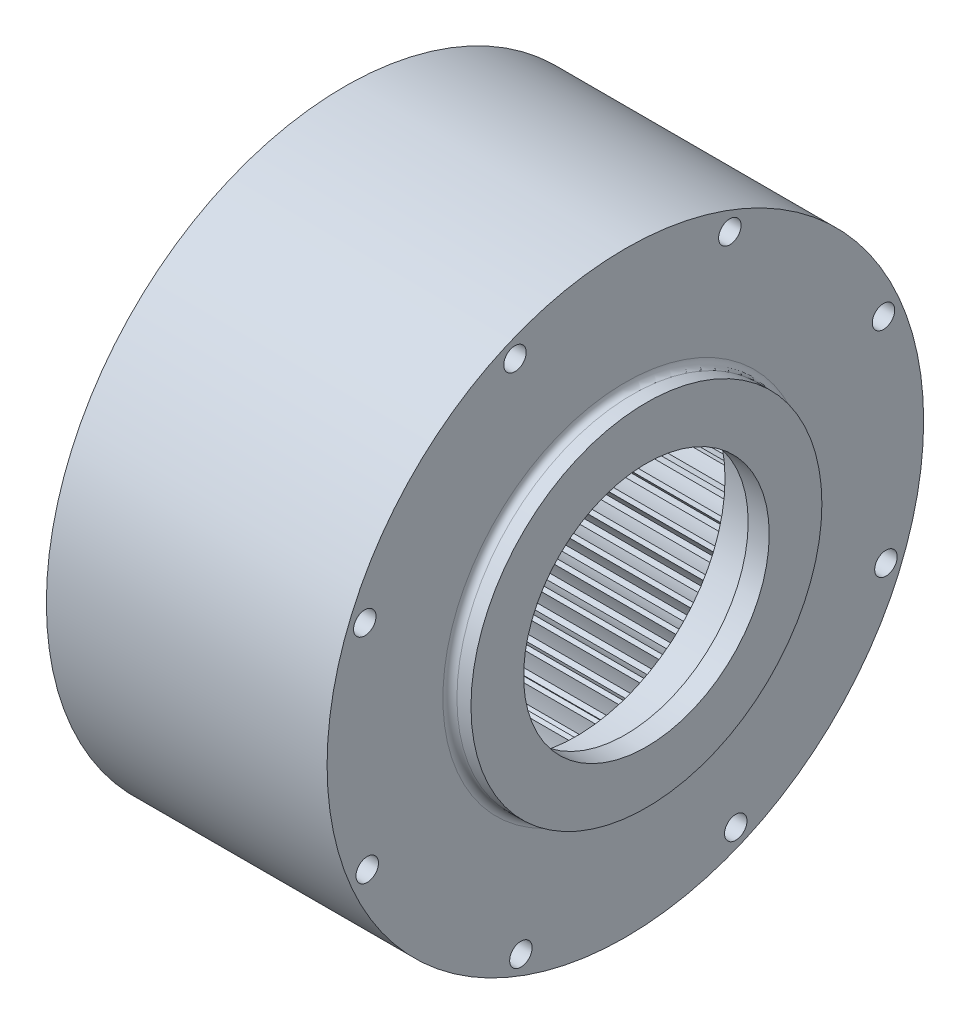
SolidWorks part; units mm, degrees
ref_plane "Plane1" through (0, 0, 0) normal (0, 0, 1) x (1, 0, 0)
ref_plane "Plane2" through (0, 0, 0) normal (0, 1, 0) x (1, 0, 0)
ref_plane "Plane3" through (0, 0, 0) normal (1, 0, 0) x (0, 0, -1)
sketch "HoldingSke" plane through (0, 0, 0) normal (0, 1, 0) x (1, 0, 0)
  line L0 (0, 0) -> (0.342, -0.9397)
  line L1 (-15, 0) -> (100, 0) construction
  line L2 (0, 0) -> (-2.1039, 2.3779)
  line L3 (0, 0) -> (-11.863, 4.5341)
  line L4 (0, 0) -> (2.9537, 8.1152)
  line L5 (0, 0) -> (-23.7986, -8.8762)
  line L6 (0, 0) -> (-10.5278, -7.1032)
  line L7 (-2.1039, 2.3779) -> (3.3635, 27.1825)
  line L8 (-76.2, 3.3779) -> (-54.61, 3.3779)
  line L9 (-71.009, 38.7566) -> (-53.1078, 45.2721)
  line L10 (-76.2, 71.12) -> (104.1128, 71.12)
  line L11 (0, 0) -> (-30, 0)
  line L12 (-76.2, 101.6) -> (-76.162, 101.6)
  line L13 (24.9733, 27.94) -> (52.9518, 28.4284)
  line L14 (24.9733, 27.94) -> (24.9743, 27.94)
  line L15 (24.9733, 27.94) -> (100.4006, 29.5858)
  circle A0 centre (0, 0) radius 42.5
  circle A1 centre (0, 0) radius 12.7
  circle A2 centre (0, 0) radius 12.7
  dimension "MHD" = 25.4
  dimension "Hub_dia" = 25.4
  dimension "Diameter" = 85
  dimension "Num_teeth" = 70
  dimension "Pitch" = 1
  dimension "Overall_len" = 25.4
  dimension "Show_teeth" = 70
  dimension "Thickness" = 12.7
  dimension "OAL" = 25.4001
  dimension "T_dim" = 21.59
  dimension "Ap" = 20
  dimension "H" = 19.05
  dimension "Pitch_radius" = 180.3128
  dimension "Width" = 30
  dimension "Backlash" = 0.038
  dimension "Addendum_fac" = 1
  dimension "Dedendum_fac" = 1.25
  dimension "Clearance_fac" = 0.25
  dimension "Dedendum_add" = 0.001
  dimension "Module" = 1
sketch "BasProSke" plane through (0, 0, 0) normal (0, 1, 0) x (1, 0, 0)
  line L0 (-10, 0) -> (60, 0) construction
  line L1 (0, 34) -> (0, 42.5)
  line L2 (0, 34) -> (30, 34)
  line L3 (30, 34) -> (30, 42.5)
  line L4 (30, 42.5) -> (0, 42.5)
  dimension "Diameter" = 85
  dimension "Thickness" = 30
  dimension "Inside_diameter" = 68
revolve "Base-Revolve" add sketch "BasProSke" angle 360 about L0
sketch "TooCutSke" plane through (0, 0, 0) normal (1, 0, 0) x (0, 0, -1)
  line L3 (0.8803, 34.9889) -> (0.8803, 53.6633) construction
  line L4 (0, 0) -> (0, 59.563) construction
  line L5 (0, 0) -> (-3.0655, 68.2587) construction
  line L6 (-15.5382, 28.9323) -> (36.4767, 31.2683) construction
  circle A0 centre (0, 0) radius 35 construction
  circle A1 centre (0, 0) radius 36.251 construction
  circle A2 centre (0, 0) radius 29.6003 construction
  circle A3 centre (0, 0) radius 33.9746 construction
  arc A4 (1.2263, 33.9525) -> (0.3588, 36.2492) centre (-15.5382, 28.9323) ccw
  arc A5 (1.2263, 33.9525) -> (-1.2263, 33.9525) centre (0, 0) ccw
  arc A6 (0.3588, 36.2492) -> (-0.3588, 36.2492) centre (0, 0) ccw
  arc A7 (-0.3588, 36.2492) -> (-1.2263, 33.9525) centre (15.5382, 28.9323) ccw
  dimension "Pitch_dia" = 70
  dimension "Base_dia" = 59.2006
  dimension "Root_dia" = 72.502
  dimension "Overcut_dia" = 67.9492
  dimension "Flank_rad" = 17.5
  dimension "Half_ang" = 2.571
  dimension "Half_CT" = 0.8803
extrude "ToothCut" cut sketch "TooCutSke" along normal through all
fillet "Breaks" [suppressed] radius 0.1
fillet "RootFillets" [suppressed] radius 0.251
pattern_circular "TeethCuts" count 70 every 5.143 about axis through (-10, 0, 0) along (1, 0, 0) of "RootFillets", "Breaks", "ToothCut"
sketch "Sketch1" plane through (30, 0, 0) normal (1, 0, 0) x (0, 0, -1)
  circle A1 centre (0, 0) radius 21.2
  circle A2 centre (0, 0) radius 42.5 construction
  circle A3 centre (0, 0) radius 42.5
extrude "Boss-Extrude1" add sketch "Sketch1" along normal blind 7
sketch "Sketch2" plane through (37, 0, 0) normal (1, 0, 0) x (0, 0, -1)
  circle A0 centre (0, 0) radius 25
  circle A1 centre (0, 0) radius 17.5
extrude "Boss-Extrude2" add sketch "Sketch2" along normal blind 3
fillet "Fillet1" radius 1 1 edges at (37, 0, -25)
sketch "Sketch4" plane through (0, 0, 0) normal (-1, 0, 0) x (0, 0, 1)
  arc A0 (-21.0165, 29.5371) -> (-21.597, 29.1154) centre (0, 0) ccw construction
  circle A1 centre (0, 0) radius 42.5
  circle A2 centre (0, 0) radius 42.5
  arc A3 (-21.597, 29.1154) -> (-20.9577, 26.7726) centre (-4.4353, 32.5399) ccw construction
  arc A4 (-20.9577, 26.7726) -> (-21.4379, 26.3897) centre (0, 0) ccw construction
  arc A5 (-21.4379, 26.3897) -> (-23.5796, 27.5343) centre (-30.7371, 11.5649) ccw construction
  arc A6 (-23.5796, 27.5343) -> (-24.1199, 27.0622) centre (0, 0) ccw construction
  arc A7 (-23.5796, 27.5343) -> (-24.1199, 27.0622) centre (0, 0) ccw construction
  arc A8 (-24.1199, 27.0622) -> (-23.2732, 24.7862) centre (-7.3343, 32.0113) ccw construction
  arc A9 (-23.2732, 24.7862) -> (-23.7171, 24.3618) centre (0, 0) ccw construction
  arc A10 (-23.7171, 24.3618) -> (-25.9528, 25.3098) centre (-31.65, 8.7631) ccw construction
  arc A11 (-25.9528, 25.3098) -> (-26.4487, 24.7912) centre (0, 0) ccw construction
  arc A12 (18.2842, -31.3021) -> (18.9002, -30.9341) centre (0, 0) ccw construction
  arc A13 (18.9002, -30.9341) -> (18.4735, -28.5435) centre (1.5006, -32.8064) ccw construction
  arc A14 (18.4735, -28.5435) -> (18.986, -28.2052) centre (0, 0) ccw construction
  arc A15 (18.986, -28.2052) -> (21.0165, -29.5371) centre (29.5767, -14.2736) ccw construction
  arc A16 (21.0165, -29.5371) -> (21.597, -29.1154) centre (0, 0) ccw construction
  arc A17 (21.0165, -29.5371) -> (21.597, -29.1154) centre (0, 0) ccw construction
  arc A18 (21.597, -29.1154) -> (20.9577, -26.7726) centre (4.4353, -32.5399) ccw construction
  arc A19 (20.9577, -26.7726) -> (21.4379, -26.3897) centre (0, 0) ccw construction
  arc A20 (21.4379, -26.3897) -> (23.5796, -27.5343) centre (30.7371, -11.5649) ccw construction
  arc A21 (23.5796, -27.5343) -> (24.1199, -27.0622) centre (0, 0) ccw construction
  arc A22 (-15.4047, 32.8151) -> (-16.0512, 32.5038) centre (0, 0) ccw construction
  arc A23 (-16.0512, 32.5038) -> (-15.8405, 30.0845) centre (1.4462, 32.8089) ccw construction
  arc A24 (-15.8405, 30.0845) -> (-16.3813, 29.7935) centre (0, 0) ccw construction
  arc A25 (-16.3813, 29.7935) -> (-18.2842, 31.3021) centre (-28.1781, 16.8674) ccw construction
  arc A26 (-18.2842, 31.3021) -> (-18.9002, 30.9341) centre (0, 0) ccw construction
  arc A27 (-18.2842, 31.3021) -> (-18.9002, 30.9341) centre (0, 0) ccw construction
  arc A28 (-18.9002, 30.9341) -> (-18.4735, 28.5435) centre (-1.5006, 32.8064) ccw construction
  arc A29 (-18.4735, 28.5435) -> (-18.986, 28.2052) centre (0, 0) ccw construction
  arc A30 (-18.986, 28.2052) -> (-21.0165, 29.5371) centre (-29.5767, 14.2736) ccw construction
  arc A31 (-21.0165, 29.5371) -> (-21.597, 29.1154) centre (0, 0) ccw construction
  arc A32 (12.4012, -34.0639) -> (13.073, -33.8117) centre (0, 0) ccw construction
  arc A33 (13.073, -33.8117) -> (13.08, -31.3833) centre (-4.3813, -32.5472) ccw construction
  arc A34 (13.08, -31.3833) -> (13.6447, -31.142) centre (0, 0) ccw construction
  arc A35 (13.6447, -31.142) -> (15.4047, -32.8151) centre (26.5527, -19.3254) ccw construction
  arc A36 (15.4047, -32.8151) -> (16.0512, -32.5038) centre (0, 0) ccw construction
  arc A37 (15.4047, -32.8151) -> (16.0512, -32.5038) centre (0, 0) ccw construction
  arc A38 (16.0512, -32.5038) -> (15.8405, -30.0845) centre (-1.4462, -32.8089) ccw construction
  arc A39 (15.8405, -30.0845) -> (16.3813, -29.7935) centre (0, 0) ccw construction
  arc A40 (16.3813, -29.7935) -> (18.2842, -31.3021) centre (28.1781, -16.8674) ccw construction
  arc A41 (18.2842, -31.3021) -> (18.9002, -30.9341) centre (0, 0) ccw construction
  arc A42 (-9.2978, 35.0384) -> (-9.9895, 34.8475) centre (0, 0) ccw construction
  arc A43 (-9.9895, 34.8475) -> (-10.2141, 32.4295) centre (7.2812, 32.0234) ccw construction
  arc A44 (-10.2141, 32.4295) -> (-10.7982, 32.2397) centre (0, 0) ccw construction
  arc A45 (-10.7982, 32.2397) -> (-12.4012, 34.0639) centre (-24.7135, 21.6277) ccw construction
  arc A46 (-12.4012, 34.0639) -> (-13.073, 33.8117) centre (0, 0) ccw construction
  arc A47 (-12.4012, 34.0639) -> (-13.073, 33.8117) centre (0, 0) ccw construction
  arc A48 (-13.073, 33.8117) -> (-13.08, 31.3833) centre (4.3813, 32.5472) ccw construction
  arc A49 (-13.08, 31.3833) -> (-13.6447, 31.142) centre (0, 0) ccw construction
  arc A50 (-13.6447, 31.142) -> (-15.4047, 32.8151) centre (-26.5527, 19.3254) ccw construction
  arc A51 (-15.4047, 32.8151) -> (-16.0512, 32.5038) centre (0, 0) ccw construction
  arc A52 (6.1195, -35.7307) -> (6.8256, -35.6026) centre (0, 0) ccw construction
  arc A53 (6.8256, -35.6026) -> (7.266, -33.2145) centre (-10.1224, -31.2418) ccw construction
  arc A54 (7.266, -33.2145) -> (7.8648, -33.0779) centre (0, 0) ccw construction
  arc A55 (7.8648, -33.0779) -> (9.2978, -35.0384) centre (22.6753, -23.756) ccw construction
  arc A56 (9.2978, -35.0384) -> (9.9895, -34.8475) centre (0, 0) ccw construction
  arc A57 (9.2978, -35.0384) -> (9.9895, -34.8475) centre (0, 0) ccw construction
  arc A58 (9.9895, -34.8475) -> (10.2141, -32.4295) centre (-7.2812, -32.0234) ccw construction
  arc A59 (10.2141, -32.4295) -> (10.7982, -32.2397) centre (0, 0) ccw construction
  arc A60 (10.7982, -32.2397) -> (12.4012, -34.0639) centre (24.7135, -21.6277) ccw construction
  arc A61 (12.4012, -34.0639) -> (13.073, -33.8117) centre (0, 0) ccw construction
  arc A62 (-2.892, 36.1355) -> (-3.6067, 36.0711) centre (0, 0) ccw construction
  arc A63 (-3.6067, 36.0711) -> (-4.2595, 33.7321) centre (12.8822, 30.2087) ccw construction
  arc A64 (-4.2595, 33.7321) -> (-4.868, 33.6497) centre (0, 0) ccw construction
  arc A65 (-4.868, 33.6497) -> (-6.1195, 35.7307) centre (-20.4545, 25.6929) ccw construction
  arc A66 (-6.1195, 35.7307) -> (-6.8256, 35.6026) centre (0, 0) ccw construction
  arc A67 (-6.1195, 35.7307) -> (-6.8256, 35.6026) centre (0, 0) ccw construction
  arc A68 (-6.8256, 35.6026) -> (-7.266, 33.2145) centre (10.1224, 31.2418) ccw construction
  arc A69 (-7.266, 33.2145) -> (-7.8648, 33.0779) centre (0, 0) ccw construction
  arc A70 (-7.8648, 33.0779) -> (-9.2978, 35.0384) centre (-22.6753, 23.756) ccw construction
  arc A71 (-9.2978, 35.0384) -> (-9.9895, 34.8475) centre (0, 0) ccw construction
  arc A72 (-0.3588, -36.2492) -> (0.3588, -36.2492) centre (0, 0) ccw construction
  arc A73 (0.3588, -36.2492) -> (1.2186, -33.9782) centre (-15.5382, -28.9323) ccw construction
  arc A74 (1.2186, -33.9782) -> (1.8321, -33.9506) centre (0, 0) ccw construction
  arc A75 (1.8321, -33.9506) -> (2.892, -36.1355) centre (18.0691, -27.423) ccw construction
  arc A76 (2.892, -36.1355) -> (3.6067, -36.0711) centre (0, 0) ccw construction
  arc A77 (2.892, -36.1355) -> (3.6067, -36.0711) centre (0, 0) ccw construction
  arc A78 (3.6067, -36.0711) -> (4.2595, -33.7321) centre (-12.8822, -30.2087) ccw construction
  arc A79 (4.2595, -33.7321) -> (4.868, -33.6497) centre (0, 0) ccw construction
  arc A80 (4.868, -33.6497) -> (6.1195, -35.7307) centre (20.4545, -25.6929) ccw construction
  arc A81 (6.1195, -35.7307) -> (6.8256, -35.6026) centre (0, 0) ccw construction
  arc A82 (3.6067, 36.0711) -> (2.892, 36.1355) centre (0, 0) ccw construction
  arc A83 (2.892, 36.1355) -> (1.8321, 33.9506) centre (18.0691, 27.423) ccw construction
  arc A84 (1.8321, 33.9506) -> (1.2186, 33.9782) centre (0, 0) ccw construction
  arc A85 (1.2186, 33.9782) -> (0.3588, 36.2492) centre (-15.5382, 28.9323) ccw construction
  arc A86 (0.3588, 36.2492) -> (-0.3588, 36.2492) centre (0, 0) ccw construction
  arc A87 (0.3588, 36.2492) -> (-0.3588, 36.2492) centre (0, 0) ccw construction
  arc A88 (-0.3588, 36.2492) -> (-1.2186, 33.9782) centre (15.5382, 28.9323) ccw construction
  arc A89 (-1.2186, 33.9782) -> (-1.8321, 33.9506) centre (0, 0) ccw construction
  arc A90 (-1.8321, 33.9506) -> (-2.892, 36.1355) centre (-18.0691, 27.423) ccw construction
  arc A91 (-2.892, 36.1355) -> (-3.6067, 36.0711) centre (0, 0) ccw construction
  arc A92 (-6.8256, -35.6026) -> (-6.1195, -35.7307) centre (0, 0) ccw construction
  arc A93 (-6.1195, -35.7307) -> (-4.868, -33.6497) centre (-20.4545, -25.6929) ccw construction
  arc A94 (-4.868, -33.6497) -> (-4.2595, -33.7321) centre (0, 0) ccw construction
  arc A95 (-4.2595, -33.7321) -> (-3.6067, -36.0711) centre (12.8822, -30.2087) ccw construction
  arc A96 (-3.6067, -36.0711) -> (-2.892, -36.1355) centre (0, 0) ccw construction
  arc A97 (-3.6067, -36.0711) -> (-2.892, -36.1355) centre (0, 0) ccw construction
  arc A98 (-2.892, -36.1355) -> (-1.8321, -33.9506) centre (-18.0691, -27.423) ccw construction
  arc A99 (-1.8321, -33.9506) -> (-1.2186, -33.9782) centre (0, 0) ccw construction
  arc A100 (-1.2186, -33.9782) -> (-0.3588, -36.2492) centre (15.5382, -28.9323) ccw construction
  arc A101 (-0.3588, -36.2492) -> (0.3588, -36.2492) centre (0, 0) ccw construction
  arc A102 (9.9895, 34.8475) -> (9.2978, 35.0384) centre (0, 0) ccw construction
  arc A103 (9.2978, 35.0384) -> (7.8648, 33.0779) centre (22.6753, 23.756) ccw construction
  arc A104 (7.8648, 33.0779) -> (7.266, 33.2145) centre (0, 0) ccw construction
  arc A105 (7.266, 33.2145) -> (6.8256, 35.6026) centre (-10.1224, 31.2418) ccw construction
  arc A106 (6.8256, 35.6026) -> (6.1195, 35.7307) centre (0, 0) ccw construction
  arc A107 (6.8256, 35.6026) -> (6.1195, 35.7307) centre (0, 0) ccw construction
  arc A108 (6.1195, 35.7307) -> (4.868, 33.6497) centre (20.4545, 25.6929) ccw construction
  arc A109 (4.868, 33.6497) -> (4.2595, 33.7321) centre (0, 0) ccw construction
  arc A110 (4.2595, 33.7321) -> (3.6067, 36.0711) centre (-12.8822, 30.2087) ccw construction
  arc A111 (3.6067, 36.0711) -> (2.892, 36.1355) centre (0, 0) ccw construction
  arc A112 (-13.073, -33.8117) -> (-12.4012, -34.0639) centre (0, 0) ccw construction
  arc A113 (-12.4012, -34.0639) -> (-10.7982, -32.2397) centre (-24.7135, -21.6277) ccw construction
  arc A114 (-10.7982, -32.2397) -> (-10.2141, -32.4295) centre (0, 0) ccw construction
  arc A115 (-10.2141, -32.4295) -> (-9.9895, -34.8475) centre (7.2812, -32.0234) ccw construction
  arc A116 (-9.9895, -34.8475) -> (-9.2978, -35.0384) centre (0, 0) ccw construction
  arc A117 (-9.9895, -34.8475) -> (-9.2978, -35.0384) centre (0, 0) ccw construction
  arc A118 (-9.2978, -35.0384) -> (-7.8648, -33.0779) centre (-22.6753, -23.756) ccw construction
  arc A119 (-7.8648, -33.0779) -> (-7.266, -33.2145) centre (0, 0) ccw construction
  arc A120 (-7.266, -33.2145) -> (-6.8256, -35.6026) centre (10.1224, -31.2418) ccw construction
  arc A121 (-6.8256, -35.6026) -> (-6.1195, -35.7307) centre (0, 0) ccw construction
  arc A122 (16.0512, 32.5038) -> (15.4047, 32.8151) centre (0, 0) ccw construction
  arc A123 (15.4047, 32.8151) -> (13.6447, 31.142) centre (26.5527, 19.3254) ccw construction
  arc A124 (13.6447, 31.142) -> (13.08, 31.3833) centre (0, 0) ccw construction
  arc A125 (13.08, 31.3833) -> (13.073, 33.8117) centre (-4.3813, 32.5472) ccw construction
  arc A126 (13.073, 33.8117) -> (12.4012, 34.0639) centre (0, 0) ccw construction
  arc A127 (13.073, 33.8117) -> (12.4012, 34.0639) centre (0, 0) ccw construction
  arc A128 (12.4012, 34.0639) -> (10.7982, 32.2397) centre (24.7135, 21.6277) ccw construction
  arc A129 (10.7982, 32.2397) -> (10.2141, 32.4295) centre (0, 0) ccw construction
  arc A130 (10.2141, 32.4295) -> (9.9895, 34.8475) centre (-7.2812, 32.0234) ccw construction
  arc A131 (9.9895, 34.8475) -> (9.2978, 35.0384) centre (0, 0) ccw construction
  arc A132 (-18.9002, -30.9341) -> (-18.2842, -31.3021) centre (0, 0) ccw construction
  arc A133 (-18.2842, -31.3021) -> (-16.3813, -29.7935) centre (-28.1781, -16.8674) ccw construction
  arc A134 (-16.3813, -29.7935) -> (-15.8405, -30.0845) centre (0, 0) ccw construction
  arc A135 (-15.8405, -30.0845) -> (-16.0512, -32.5038) centre (1.4462, -32.8089) ccw construction
  arc A136 (-16.0512, -32.5038) -> (-15.4047, -32.8151) centre (0, 0) ccw construction
  arc A137 (-16.0512, -32.5038) -> (-15.4047, -32.8151) centre (0, 0) ccw construction
  arc A138 (-15.4047, -32.8151) -> (-13.6447, -31.142) centre (-26.5527, -19.3254) ccw construction
  arc A139 (-13.6447, -31.142) -> (-13.08, -31.3833) centre (0, 0) ccw construction
  arc A140 (-13.08, -31.3833) -> (-13.073, -33.8117) centre (4.3813, -32.5472) ccw construction
  arc A141 (-13.073, -33.8117) -> (-12.4012, -34.0639) centre (0, 0) ccw construction
  arc A142 (21.597, 29.1154) -> (21.0165, 29.5371) centre (0, 0) ccw construction
  arc A143 (21.0165, 29.5371) -> (18.986, 28.2052) centre (29.5767, 14.2736) ccw construction
  arc A144 (18.986, 28.2052) -> (18.4735, 28.5435) centre (0, 0) ccw construction
  arc A145 (18.4735, 28.5435) -> (18.9002, 30.9341) centre (1.5006, 32.8064) ccw construction
  arc A146 (18.9002, 30.9341) -> (18.2842, 31.3021) centre (0, 0) ccw construction
  arc A147 (18.9002, 30.9341) -> (18.2842, 31.3021) centre (0, 0) ccw construction
  arc A148 (18.2842, 31.3021) -> (16.3813, 29.7935) centre (28.1781, 16.8674) ccw construction
  arc A149 (16.3813, 29.7935) -> (15.8405, 30.0845) centre (0, 0) ccw construction
  arc A150 (15.8405, 30.0845) -> (16.0512, 32.5038) centre (-1.4462, 32.8089) ccw construction
  arc A151 (16.0512, 32.5038) -> (15.4047, 32.8151) centre (0, 0) ccw construction
  arc A152 (-24.1199, -27.0622) -> (-23.5796, -27.5343) centre (0, 0) ccw construction
  arc A153 (-23.5796, -27.5343) -> (-21.4379, -26.3897) centre (-30.7371, -11.5649) ccw construction
  arc A154 (-21.4379, -26.3897) -> (-20.9577, -26.7726) centre (0, 0) ccw construction
  arc A155 (-20.9577, -26.7726) -> (-21.597, -29.1154) centre (-4.4353, -32.5399) ccw construction
  arc A156 (-21.597, -29.1154) -> (-21.0165, -29.5371) centre (0, 0) ccw construction
  arc A157 (-21.597, -29.1154) -> (-21.0165, -29.5371) centre (0, 0) ccw construction
  arc A158 (-21.0165, -29.5371) -> (-18.986, -28.2052) centre (-29.5767, -14.2736) ccw construction
  arc A159 (-18.986, -28.2052) -> (-18.4735, -28.5435) centre (0, 0) ccw construction
  arc A160 (-18.4735, -28.5435) -> (-18.9002, -30.9341) centre (-1.5006, -32.8064) ccw construction
  arc A161 (-18.9002, -30.9341) -> (-18.2842, -31.3021) centre (0, 0) ccw construction
  arc A162 (26.4487, 24.7912) -> (25.9528, 25.3098) centre (0, 0) ccw construction
  arc A163 (25.9528, 25.3098) -> (23.7171, 24.3618) centre (31.65, 8.7631) ccw construction
  arc A164 (23.7171, 24.3618) -> (23.2732, 24.7862) centre (0, 0) ccw construction
  arc A165 (23.2732, 24.7862) -> (24.1199, 27.0622) centre (7.3343, 32.0113) ccw construction
  arc A166 (24.1199, 27.0622) -> (23.5796, 27.5343) centre (0, 0) ccw construction
  arc A167 (24.1199, 27.0622) -> (23.5796, 27.5343) centre (0, 0) ccw construction
  arc A168 (23.5796, 27.5343) -> (21.4379, 26.3897) centre (30.7371, 11.5649) ccw construction
  arc A169 (21.4379, 26.3897) -> (20.9577, 26.7726) centre (0, 0) ccw construction
  arc A170 (20.9577, 26.7726) -> (21.597, 29.1154) centre (4.4353, 32.5399) ccw construction
  arc A171 (21.597, 29.1154) -> (21.0165, 29.5371) centre (0, 0) ccw construction
  arc A172 (-28.5645, -22.3205) -> (-28.1171, -22.8815) centre (0, 0) ccw construction
  arc A173 (-28.1171, -22.8815) -> (-25.8054, -22.1378) centre (-32.3081, -5.8908) ccw construction
  arc A174 (-25.8054, -22.1378) -> (-25.4014, -22.6002) centre (0, 0) ccw construction
  arc A175 (-25.4014, -22.6002) -> (-26.4487, -24.7912) centre (-10.1743, -31.225) ccw construction
  arc A176 (-26.4487, -24.7912) -> (-25.9528, -25.3098) centre (0, 0) ccw construction
  arc A177 (-26.4487, -24.7912) -> (-25.9528, -25.3098) centre (0, 0) ccw construction
  arc A178 (-25.9528, -25.3098) -> (-23.7171, -24.3618) centre (-31.65, -8.7631) ccw construction
  arc A179 (-23.7171, -24.3618) -> (-23.2732, -24.7862) centre (0, 0) ccw construction
  arc A180 (-23.2732, -24.7862) -> (-24.1199, -27.0622) centre (-7.3343, -32.0113) ccw construction
  arc A181 (-24.1199, -27.0622) -> (-23.5796, -27.5343) centre (0, 0) ccw construction
  arc A182 (30.4503, 19.6702) -> (30.055, 20.269) centre (0, 0) ccw construction
  arc A183 (30.055, 20.269) -> (27.6859, 19.7355) centre (32.7061, 2.971) ccw construction
  arc A184 (27.6859, 19.7355) -> (27.325, 20.2323) centre (0, 0) ccw construction
  arc A185 (27.325, 20.2323) -> (28.5645, 22.3205) centre (12.9323, 30.1873) ccw construction
  arc A186 (28.5645, 22.3205) -> (28.1171, 22.8815) centre (0, 0) ccw construction
  arc A187 (28.5645, 22.3205) -> (28.1171, 22.8815) centre (0, 0) ccw construction
  arc A188 (28.1171, 22.8815) -> (25.8054, 22.1378) centre (32.3081, 5.8908) ccw construction
  arc A189 (25.8054, 22.1378) -> (25.4014, 22.6002) centre (0, 0) ccw construction
  arc A190 (25.4014, 22.6002) -> (26.4487, 24.7912) centre (10.1743, 31.225) ccw construction
  arc A191 (26.4487, 24.7912) -> (25.9528, 25.3098) centre (0, 0) ccw construction
  arc A192 (-32.0909, -16.8614) -> (-31.7509, -17.4933) centre (0, 0) ccw construction
  arc A193 (-31.7509, -17.4933) -> (-29.3436, -17.1743) centre (-32.8407, -0.0273) ccw construction
  arc A194 (-29.3436, -17.1743) -> (-29.0286, -17.7015) centre (0, 0) ccw construction
  arc A195 (-29.0286, -17.7015) -> (-30.4503, -19.6702) centre (-15.5862, -28.9065) ccw construction
  arc A196 (-30.4503, -19.6702) -> (-30.055, -20.269) centre (0, 0) ccw construction
  arc A197 (-30.4503, -19.6702) -> (-30.055, -20.269) centre (0, 0) ccw construction
  arc A198 (-30.055, -20.269) -> (-27.6859, -19.7355) centre (-32.7061, -2.971) ccw construction
  arc A199 (-27.6859, -19.7355) -> (-27.325, -20.2323) centre (0, 0) ccw construction
  arc A200 (-27.325, -20.2323) -> (-28.5645, -22.3205) centre (-12.9323, -30.1873) ccw construction
  arc A201 (-28.5645, -22.3205) -> (-28.1171, -22.8815) centre (0, 0) ccw construction
  arc A202 (33.4732, 13.917) -> (33.1912, 14.5768) centre (0, 0) ccw construction
  arc A203 (33.1912, 14.5768) -> (30.7649, 14.4748) centre (32.711, -2.9167) ccw construction
  arc A204 (30.7649, 14.4748) -> (30.4985, 15.0281) centre (0, 0) ccw construction
  arc A205 (30.4985, 15.0281) -> (32.0909, 16.8614) centre (18.1146, 27.393) ccw construction
  arc A206 (32.0909, 16.8614) -> (31.7509, 17.4933) centre (0, 0) ccw construction
  arc A207 (32.0909, 16.8614) -> (31.7509, 17.4933) centre (0, 0) ccw construction
  arc A208 (31.7509, 17.4933) -> (29.3436, 17.1743) centre (32.8407, 0.0273) ccw construction
  arc A209 (29.3436, 17.1743) -> (29.0286, 17.7015) centre (0, 0) ccw construction
  arc A210 (29.0286, 17.7015) -> (30.4503, 19.6702) centre (15.5862, 28.9065) ccw construction
  arc A211 (30.4503, 19.6702) -> (30.055, 20.269) centre (0, 0) ccw construction
  arc A212 (-34.5859, -10.8604) -> (-34.3642, -11.5428) centre (0, 0) ccw construction
  arc A213 (-34.3642, -11.5428) -> (-31.9386, -11.6588) centre (-32.3178, 5.8371) ccw construction
  arc A214 (-31.9386, -11.6588) -> (-31.7228, -12.2337) centre (0, 0) ccw construction
  arc A215 (-31.7228, -12.2337) -> (-33.4732, -13.917) centre (-20.4972, -25.6589) ccw construction
  arc A216 (-33.4732, -13.917) -> (-33.1912, -14.5768) centre (0, 0) ccw construction
  arc A217 (-33.4732, -13.917) -> (-33.1912, -14.5768) centre (0, 0) ccw construction
  arc A218 (-33.1912, -14.5768) -> (-30.7649, -14.4748) centre (-32.711, 2.9167) ccw construction
  arc A219 (-30.7649, -14.4748) -> (-30.4985, -15.0281) centre (0, 0) ccw construction
  arc A220 (-30.4985, -15.0281) -> (-32.0909, -16.8614) centre (-18.1146, -27.393) ccw construction
  arc A221 (-32.0909, -16.8614) -> (-31.7509, -17.4933) centre (0, 0) ccw construction
  arc A222 (35.4202, 7.7164) -> (35.2605, 8.416) centre (0, 0) ccw construction
  arc A223 (35.2605, 8.416) -> (32.8551, 8.7489) centre (31.6645, -8.7106) ccw construction
  arc A224 (32.8551, 8.7489) -> (32.6917, 9.3409) centre (0, 0) ccw construction
  arc A225 (32.6917, 9.3409) -> (34.5859, 10.8604) centre (22.7147, 23.7183) ccw construction
  arc A226 (34.5859, 10.8604) -> (34.3642, 11.5428) centre (0, 0) ccw construction
  arc A227 (34.5859, 10.8604) -> (34.3642, 11.5428) centre (0, 0) ccw construction
  arc A228 (34.3642, 11.5428) -> (31.9386, 11.6588) centre (32.3178, -5.8371) ccw construction
  arc A229 (31.9386, 11.6588) -> (31.7228, 12.2337) centre (0, 0) ccw construction
  arc A230 (31.7228, 12.2337) -> (33.4732, 13.917) centre (20.4972, 25.6589) ccw construction
  arc A231 (33.4732, 13.917) -> (33.1912, 14.5768) centre (0, 0) ccw construction
  arc A232 (-35.9693, -4.5103) -> (-35.873, -5.2214) centre (0, 0) ccw construction
  arc A233 (-35.873, -5.2214) -> (-33.5071, -5.7686) centre (-30.7562, 11.5139) ccw construction
  arc A234 (-33.5071, -5.7686) -> (-33.3974, -6.3728) centre (0, 0) ccw construction
  arc A235 (-33.3974, -6.3728) -> (-35.4202, -7.7164) centre (-24.7494, -21.5867) ccw construction
  arc A236 (-35.4202, -7.7164) -> (-35.2605, -8.416) centre (0, 0) ccw construction
  arc A237 (-35.4202, -7.7164) -> (-35.2605, -8.416) centre (0, 0) ccw construction
  arc A238 (-35.2605, -8.416) -> (-32.8551, -8.7489) centre (-31.6645, 8.7106) ccw construction
  arc A239 (-32.8551, -8.7489) -> (-32.6917, -9.3409) centre (0, 0) ccw construction
  arc A240 (-32.6917, -9.3409) -> (-34.5859, -10.8604) centre (-22.7147, -23.7183) ccw construction
  arc A241 (-34.5859, -10.8604) -> (-34.3642, -11.5428) centre (0, 0) ccw construction
  arc A242 (36.2288, 1.2679) -> (36.1966, 1.9847) centre (0, 0) ccw construction
  arc A243 (36.1966, 1.9847) -> (33.8893, 2.7418) centre (29.6003, -14.2245) ccw construction
  arc A244 (33.8893, 2.7418) -> (33.8342, 3.3534) centre (0, 0) ccw construction
  arc A245 (33.8342, 3.3534) -> (35.9693, 4.5103) centre (26.5847, 19.2812) ccw construction
  arc A246 (35.9693, 4.5103) -> (35.873, 5.2214) centre (0, 0) ccw construction
  arc A247 (35.9693, 4.5103) -> (35.873, 5.2214) centre (0, 0) ccw construction
  arc A248 (35.873, 5.2214) -> (33.5071, 5.7686) centre (30.7562, -11.5139) ccw construction
  arc A249 (33.5071, 5.7686) -> (33.3974, 6.3728) centre (0, 0) ccw construction
  arc A250 (33.3974, 6.3728) -> (35.4202, 7.7164) centre (24.7494, 21.5867) ccw construction
  arc A251 (35.4202, 7.7164) -> (35.2605, 8.416) centre (0, 0) ccw construction
  arc A252 (-36.1966, 1.9847) -> (-36.2288, 1.2679) centre (0, 0) ccw construction
  arc A253 (-36.2288, 1.2679) -> (-33.9986, 0.3071) centre (-28.2061, 16.8206) ccw construction
  arc A254 (-33.9986, 0.3071) -> (-33.9986, -0.3071) centre (0, 0) ccw construction
  arc A255 (-33.9986, -0.3071) -> (-36.2288, -1.2679) centre (-28.2061, -16.8206) ccw construction
  arc A256 (-36.2288, -1.2679) -> (-36.1966, -1.9847) centre (0, 0) ccw construction
  arc A257 (-36.2288, -1.2679) -> (-36.1966, -1.9847) centre (0, 0) ccw construction
  arc A258 (-36.1966, -1.9847) -> (-33.8893, -2.7418) centre (-29.6003, 14.2245) ccw construction
  arc A259 (-33.8893, -2.7418) -> (-33.8342, -3.3534) centre (0, 0) ccw construction
  arc A260 (-33.8342, -3.3534) -> (-35.9693, -4.5103) centre (-26.5847, -19.2812) ccw construction
  arc A261 (-35.9693, -4.5103) -> (-35.873, -5.2214) centre (0, 0) ccw construction
  arc A262 (35.873, -5.2214) -> (35.9693, -4.5103) centre (0, 0) ccw construction
  arc A263 (35.9693, -4.5103) -> (33.8342, -3.3534) centre (26.5847, -19.2812) ccw construction
  arc A264 (33.8342, -3.3534) -> (33.8893, -2.7418) centre (0, 0) ccw construction
  arc A265 (33.8893, -2.7418) -> (36.1966, -1.9847) centre (29.6003, 14.2245) ccw construction
  arc A266 (36.1966, -1.9847) -> (36.2288, -1.2679) centre (0, 0) ccw construction
  arc A267 (36.1966, -1.9847) -> (36.2288, -1.2679) centre (0, 0) ccw construction
  arc A268 (36.2288, -1.2679) -> (33.9986, -0.3071) centre (28.2061, -16.8206) ccw construction
  arc A269 (33.9986, -0.3071) -> (33.9986, 0.3071) centre (0, 0) ccw construction
  arc A270 (33.9986, 0.3071) -> (36.2288, 1.2679) centre (28.2061, 16.8206) ccw construction
  arc A271 (36.2288, 1.2679) -> (36.1966, 1.9847) centre (0, 0) ccw construction
  arc A272 (-35.2605, 8.416) -> (-35.4202, 7.7164) centre (0, 0) ccw construction
  arc A273 (-35.4202, 7.7164) -> (-33.3974, 6.3728) centre (-24.7494, 21.5867) ccw construction
  arc A274 (-33.3974, 6.3728) -> (-33.5071, 5.7686) centre (0, 0) ccw construction
  arc A275 (-33.5071, 5.7686) -> (-35.873, 5.2214) centre (-30.7562, -11.5139) ccw construction
  arc A276 (-35.873, 5.2214) -> (-35.9693, 4.5103) centre (0, 0) ccw construction
  arc A277 (-35.873, 5.2214) -> (-35.9693, 4.5103) centre (0, 0) ccw construction
  arc A278 (-35.9693, 4.5103) -> (-33.8342, 3.3534) centre (-26.5847, 19.2812) ccw construction
  arc A279 (-33.8342, 3.3534) -> (-33.8893, 2.7418) centre (0, 0) ccw construction
  arc A280 (-33.8893, 2.7418) -> (-36.1966, 1.9847) centre (-29.6003, -14.2245) ccw construction
  arc A281 (-36.1966, 1.9847) -> (-36.2288, 1.2679) centre (0, 0) ccw construction
  arc A282 (34.3642, -11.5428) -> (34.5859, -10.8604) centre (0, 0) ccw construction
  arc A283 (34.5859, -10.8604) -> (32.6917, -9.3409) centre (22.7147, -23.7183) ccw construction
  arc A284 (32.6917, -9.3409) -> (32.8551, -8.7489) centre (0, 0) ccw construction
  arc A285 (32.8551, -8.7489) -> (35.2605, -8.416) centre (31.6645, 8.7106) ccw construction
  arc A286 (35.2605, -8.416) -> (35.4202, -7.7164) centre (0, 0) ccw construction
  arc A287 (35.2605, -8.416) -> (35.4202, -7.7164) centre (0, 0) ccw construction
  arc A288 (35.4202, -7.7164) -> (33.3974, -6.3728) centre (24.7494, -21.5867) ccw construction
  arc A289 (33.3974, -6.3728) -> (33.5071, -5.7686) centre (0, 0) ccw construction
  arc A290 (33.5071, -5.7686) -> (35.873, -5.2214) centre (30.7562, 11.5139) ccw construction
  arc A291 (35.873, -5.2214) -> (35.9693, -4.5103) centre (0, 0) ccw construction
  arc A292 (-33.1912, 14.5768) -> (-33.4732, 13.917) centre (0, 0) ccw construction
  arc A293 (-33.4732, 13.917) -> (-31.7228, 12.2337) centre (-20.4972, 25.6589) ccw construction
  arc A294 (-31.7228, 12.2337) -> (-31.9386, 11.6588) centre (0, 0) ccw construction
  arc A295 (-31.9386, 11.6588) -> (-34.3642, 11.5428) centre (-32.3178, -5.8371) ccw construction
  arc A296 (-34.3642, 11.5428) -> (-34.5859, 10.8604) centre (0, 0) ccw construction
  arc A297 (-34.3642, 11.5428) -> (-34.5859, 10.8604) centre (0, 0) ccw construction
  arc A298 (-34.5859, 10.8604) -> (-32.6917, 9.3409) centre (-22.7147, 23.7183) ccw construction
  arc A299 (-32.6917, 9.3409) -> (-32.8551, 8.7489) centre (0, 0) ccw construction
  arc A300 (-32.8551, 8.7489) -> (-35.2605, 8.416) centre (-31.6645, -8.7106) ccw construction
  arc A301 (-35.2605, 8.416) -> (-35.4202, 7.7164) centre (0, 0) ccw construction
  arc A302 (31.7509, -17.4933) -> (32.0909, -16.8614) centre (0, 0) ccw construction
  arc A303 (32.0909, -16.8614) -> (30.4985, -15.0281) centre (18.1146, -27.393) ccw construction
  arc A304 (30.4985, -15.0281) -> (30.7649, -14.4748) centre (0, 0) ccw construction
  arc A305 (30.7649, -14.4748) -> (33.1912, -14.5768) centre (32.711, 2.9167) ccw construction
  arc A306 (33.1912, -14.5768) -> (33.4732, -13.917) centre (0, 0) ccw construction
  arc A307 (33.1912, -14.5768) -> (33.4732, -13.917) centre (0, 0) ccw construction
  arc A308 (33.4732, -13.917) -> (31.7228, -12.2337) centre (20.4972, -25.6589) ccw construction
  arc A309 (31.7228, -12.2337) -> (31.9386, -11.6588) centre (0, 0) ccw construction
  arc A310 (31.9386, -11.6588) -> (34.3642, -11.5428) centre (32.3178, 5.8371) ccw construction
  arc A311 (34.3642, -11.5428) -> (34.5859, -10.8604) centre (0, 0) ccw construction
  arc A312 (-30.055, 20.269) -> (-30.4503, 19.6702) centre (0, 0) ccw construction
  arc A313 (-30.4503, 19.6702) -> (-29.0286, 17.7015) centre (-15.5862, 28.9065) ccw construction
  arc A314 (-29.0286, 17.7015) -> (-29.3436, 17.1743) centre (0, 0) ccw construction
  arc A315 (-29.3436, 17.1743) -> (-31.7509, 17.4933) centre (-32.8407, 0.0273) ccw construction
  arc A316 (-31.7509, 17.4933) -> (-32.0909, 16.8614) centre (0, 0) ccw construction
  arc A317 (-31.7509, 17.4933) -> (-32.0909, 16.8614) centre (0, 0) ccw construction
  arc A318 (-32.0909, 16.8614) -> (-30.4985, 15.0281) centre (-18.1146, 27.393) ccw construction
  arc A319 (-30.4985, 15.0281) -> (-30.7649, 14.4748) centre (0, 0) ccw construction
  arc A320 (-30.7649, 14.4748) -> (-33.1912, 14.5768) centre (-32.711, -2.9167) ccw construction
  arc A321 (-33.1912, 14.5768) -> (-33.4732, 13.917) centre (0, 0) ccw construction
  arc A322 (28.1171, -22.8815) -> (28.5645, -22.3205) centre (0, 0) ccw construction
  arc A323 (28.5645, -22.3205) -> (27.325, -20.2323) centre (12.9323, -30.1873) ccw construction
  arc A324 (27.325, -20.2323) -> (27.6859, -19.7355) centre (0, 0) ccw construction
  arc A325 (27.6859, -19.7355) -> (30.055, -20.269) centre (32.7061, -2.971) ccw construction
  arc A326 (30.055, -20.269) -> (30.4503, -19.6702) centre (0, 0) ccw construction
  arc A327 (30.055, -20.269) -> (30.4503, -19.6702) centre (0, 0) ccw construction
  arc A328 (30.4503, -19.6702) -> (29.0286, -17.7015) centre (15.5862, -28.9065) ccw construction
  arc A329 (29.0286, -17.7015) -> (29.3436, -17.1743) centre (0, 0) ccw construction
  arc A330 (29.3436, -17.1743) -> (31.7509, -17.4933) centre (32.8407, -0.0273) ccw construction
  arc A331 (31.7509, -17.4933) -> (32.0909, -16.8614) centre (0, 0) ccw construction
  arc A332 (-25.9528, 25.3098) -> (-26.4487, 24.7912) centre (0, 0) ccw construction
  arc A333 (-26.4487, 24.7912) -> (-25.4014, 22.6002) centre (-10.1743, 31.225) ccw construction
  arc A334 (-25.4014, 22.6002) -> (-25.8054, 22.1378) centre (0, 0) ccw construction
  arc A335 (-25.8054, 22.1378) -> (-28.1171, 22.8815) centre (-32.3081, 5.8908) ccw construction
  arc A336 (-28.1171, 22.8815) -> (-28.5645, 22.3205) centre (0, 0) ccw construction
  arc A337 (-28.1171, 22.8815) -> (-28.5645, 22.3205) centre (0, 0) ccw construction
  arc A338 (-28.5645, 22.3205) -> (-27.325, 20.2323) centre (-12.9323, 30.1873) ccw construction
  arc A339 (-27.325, 20.2323) -> (-27.6859, 19.7355) centre (0, 0) ccw construction
  arc A340 (-27.6859, 19.7355) -> (-30.055, 20.269) centre (-32.7061, 2.971) ccw construction
  arc A341 (-30.055, 20.269) -> (-30.4503, 19.6702) centre (0, 0) ccw construction
  arc A342 (23.5796, -27.5343) -> (24.1199, -27.0622) centre (0, 0) ccw construction
  arc A343 (24.1199, -27.0622) -> (23.2732, -24.7862) centre (7.3343, -32.0113) ccw construction
  arc A344 (23.2732, -24.7862) -> (23.7171, -24.3618) centre (0, 0) ccw construction
  arc A345 (23.7171, -24.3618) -> (25.9528, -25.3098) centre (31.65, -8.7631) ccw construction
  arc A346 (25.9528, -25.3098) -> (26.4487, -24.7912) centre (0, 0) ccw construction
  arc A347 (25.9528, -25.3098) -> (26.4487, -24.7912) centre (0, 0) ccw construction
  arc A348 (26.4487, -24.7912) -> (25.4014, -22.6002) centre (10.1743, -31.225) ccw construction
  arc A349 (25.4014, -22.6002) -> (25.8054, -22.1378) centre (0, 0) ccw construction
  arc A350 (25.8054, -22.1378) -> (28.1171, -22.8815) centre (32.3081, -5.8908) ccw construction
  arc A351 (28.1171, -22.8815) -> (28.5645, -22.3205) centre (0, 0) ccw construction
  arc A352 (-21.0165, 29.5371) -> (-21.597, 29.1154) centre (0, 0) ccw
  arc A353 (-21.597, 29.1154) -> (-20.9577, 26.7726) centre (-4.4353, 32.5399) ccw
  arc A354 (-20.9577, 26.7726) -> (-21.4379, 26.3897) centre (0, 0) ccw
  arc A355 (-21.4379, 26.3897) -> (-23.5796, 27.5343) centre (-30.7371, 11.5649) ccw
  arc A356 (-23.5796, 27.5343) -> (-24.1199, 27.0622) centre (0, 0) ccw
  arc A357 (-23.5796, 27.5343) -> (-24.1199, 27.0622) centre (0, 0) ccw
  arc A358 (-24.1199, 27.0622) -> (-23.2732, 24.7862) centre (-7.3343, 32.0113) ccw
  arc A359 (-23.2732, 24.7862) -> (-23.7171, 24.3618) centre (0, 0) ccw
  arc A360 (-23.7171, 24.3618) -> (-25.9528, 25.3098) centre (-31.65, 8.7631) ccw
  arc A361 (-25.9528, 25.3098) -> (-26.4487, 24.7912) centre (0, 0) ccw
  arc A362 (18.2842, -31.3021) -> (18.9002, -30.9341) centre (0, 0) ccw
  arc A363 (18.9002, -30.9341) -> (18.4735, -28.5435) centre (1.5006, -32.8064) ccw
  arc A364 (18.4735, -28.5435) -> (18.986, -28.2052) centre (0, 0) ccw
  arc A365 (18.986, -28.2052) -> (21.0165, -29.5371) centre (29.5767, -14.2736) ccw
  arc A366 (21.0165, -29.5371) -> (21.597, -29.1154) centre (0, 0) ccw
  arc A367 (21.0165, -29.5371) -> (21.597, -29.1154) centre (0, 0) ccw
  arc A368 (21.597, -29.1154) -> (20.9577, -26.7726) centre (4.4353, -32.5399) ccw
  arc A369 (20.9577, -26.7726) -> (21.4379, -26.3897) centre (0, 0) ccw
  arc A370 (21.4379, -26.3897) -> (23.5796, -27.5343) centre (30.7371, -11.5649) ccw
  arc A371 (23.5796, -27.5343) -> (24.1199, -27.0622) centre (0, 0) ccw
  arc A372 (-15.4047, 32.8151) -> (-16.0512, 32.5038) centre (0, 0) ccw
  arc A373 (-16.0512, 32.5038) -> (-15.8405, 30.0845) centre (1.4462, 32.8089) ccw
  arc A374 (-15.8405, 30.0845) -> (-16.3813, 29.7935) centre (0, 0) ccw
  arc A375 (-16.3813, 29.7935) -> (-18.2842, 31.3021) centre (-28.1781, 16.8674) ccw
  arc A376 (-18.2842, 31.3021) -> (-18.9002, 30.9341) centre (0, 0) ccw
  arc A377 (-18.2842, 31.3021) -> (-18.9002, 30.9341) centre (0, 0) ccw
  arc A378 (-18.9002, 30.9341) -> (-18.4735, 28.5435) centre (-1.5006, 32.8064) ccw
  arc A379 (-18.4735, 28.5435) -> (-18.986, 28.2052) centre (0, 0) ccw
  arc A380 (-18.986, 28.2052) -> (-21.0165, 29.5371) centre (-29.5767, 14.2736) ccw
  arc A381 (-21.0165, 29.5371) -> (-21.597, 29.1154) centre (0, 0) ccw
  arc A382 (12.4012, -34.0639) -> (13.073, -33.8117) centre (0, 0) ccw
  arc A383 (13.073, -33.8117) -> (13.08, -31.3833) centre (-4.3813, -32.5472) ccw
  arc A384 (13.08, -31.3833) -> (13.6447, -31.142) centre (0, 0) ccw
  arc A385 (13.6447, -31.142) -> (15.4047, -32.8151) centre (26.5527, -19.3254) ccw
  arc A386 (15.4047, -32.8151) -> (16.0512, -32.5038) centre (0, 0) ccw
  arc A387 (15.4047, -32.8151) -> (16.0512, -32.5038) centre (0, 0) ccw
  arc A388 (16.0512, -32.5038) -> (15.8405, -30.0845) centre (-1.4462, -32.8089) ccw
  arc A389 (15.8405, -30.0845) -> (16.3813, -29.7935) centre (0, 0) ccw
  arc A390 (16.3813, -29.7935) -> (18.2842, -31.3021) centre (28.1781, -16.8674) ccw
  arc A391 (18.2842, -31.3021) -> (18.9002, -30.9341) centre (0, 0) ccw
  arc A392 (-9.2978, 35.0384) -> (-9.9895, 34.8475) centre (0, 0) ccw
  arc A393 (-9.9895, 34.8475) -> (-10.2141, 32.4295) centre (7.2812, 32.0234) ccw
  arc A394 (-10.2141, 32.4295) -> (-10.7982, 32.2397) centre (0, 0) ccw
  arc A395 (-10.7982, 32.2397) -> (-12.4012, 34.0639) centre (-24.7135, 21.6277) ccw
  arc A396 (-12.4012, 34.0639) -> (-13.073, 33.8117) centre (0, 0) ccw
  arc A397 (-12.4012, 34.0639) -> (-13.073, 33.8117) centre (0, 0) ccw
  arc A398 (-13.073, 33.8117) -> (-13.08, 31.3833) centre (4.3813, 32.5472) ccw
  arc A399 (-13.08, 31.3833) -> (-13.6447, 31.142) centre (0, 0) ccw
  arc A400 (-13.6447, 31.142) -> (-15.4047, 32.8151) centre (-26.5527, 19.3254) ccw
  arc A401 (-15.4047, 32.8151) -> (-16.0512, 32.5038) centre (0, 0) ccw
  arc A402 (6.1195, -35.7307) -> (6.8256, -35.6026) centre (0, 0) ccw
  arc A403 (6.8256, -35.6026) -> (7.266, -33.2145) centre (-10.1224, -31.2418) ccw
  arc A404 (7.266, -33.2145) -> (7.8648, -33.0779) centre (0, 0) ccw
  arc A405 (7.8648, -33.0779) -> (9.2978, -35.0384) centre (22.6753, -23.756) ccw
  arc A406 (9.2978, -35.0384) -> (9.9895, -34.8475) centre (0, 0) ccw
  arc A407 (9.2978, -35.0384) -> (9.9895, -34.8475) centre (0, 0) ccw
  arc A408 (9.9895, -34.8475) -> (10.2141, -32.4295) centre (-7.2812, -32.0234) ccw
  arc A409 (10.2141, -32.4295) -> (10.7982, -32.2397) centre (0, 0) ccw
  arc A410 (10.7982, -32.2397) -> (12.4012, -34.0639) centre (24.7135, -21.6277) ccw
  arc A411 (12.4012, -34.0639) -> (13.073, -33.8117) centre (0, 0) ccw
  arc A412 (-2.892, 36.1355) -> (-3.6067, 36.0711) centre (0, 0) ccw
  arc A413 (-3.6067, 36.0711) -> (-4.2595, 33.7321) centre (12.8822, 30.2087) ccw
  arc A414 (-4.2595, 33.7321) -> (-4.868, 33.6497) centre (0, 0) ccw
  arc A415 (-4.868, 33.6497) -> (-6.1195, 35.7307) centre (-20.4545, 25.6929) ccw
  arc A416 (-6.1195, 35.7307) -> (-6.8256, 35.6026) centre (0, 0) ccw
  arc A417 (-6.1195, 35.7307) -> (-6.8256, 35.6026) centre (0, 0) ccw
  arc A418 (-6.8256, 35.6026) -> (-7.266, 33.2145) centre (10.1224, 31.2418) ccw
  arc A419 (-7.266, 33.2145) -> (-7.8648, 33.0779) centre (0, 0) ccw
  arc A420 (-7.8648, 33.0779) -> (-9.2978, 35.0384) centre (-22.6753, 23.756) ccw
  arc A421 (-9.2978, 35.0384) -> (-9.9895, 34.8475) centre (0, 0) ccw
  arc A422 (-0.3588, -36.2492) -> (0.3588, -36.2492) centre (0, 0) ccw
  arc A423 (0.3588, -36.2492) -> (1.2186, -33.9782) centre (-15.5382, -28.9323) ccw
  arc A424 (1.2186, -33.9782) -> (1.8321, -33.9506) centre (0, 0) ccw
  arc A425 (1.8321, -33.9506) -> (2.892, -36.1355) centre (18.0691, -27.423) ccw
  arc A426 (2.892, -36.1355) -> (3.6067, -36.0711) centre (0, 0) ccw
  arc A427 (2.892, -36.1355) -> (3.6067, -36.0711) centre (0, 0) ccw
  arc A428 (3.6067, -36.0711) -> (4.2595, -33.7321) centre (-12.8822, -30.2087) ccw
  arc A429 (4.2595, -33.7321) -> (4.868, -33.6497) centre (0, 0) ccw
  arc A430 (4.868, -33.6497) -> (6.1195, -35.7307) centre (20.4545, -25.6929) ccw
  arc A431 (6.1195, -35.7307) -> (6.8256, -35.6026) centre (0, 0) ccw
  arc A432 (3.6067, 36.0711) -> (2.892, 36.1355) centre (0, 0) ccw
  arc A433 (2.892, 36.1355) -> (1.8321, 33.9506) centre (18.0691, 27.423) ccw
  arc A434 (1.8321, 33.9506) -> (1.2186, 33.9782) centre (0, 0) ccw
  arc A435 (1.2186, 33.9782) -> (0.3588, 36.2492) centre (-15.5382, 28.9323) ccw
  arc A436 (0.3588, 36.2492) -> (-0.3588, 36.2492) centre (0, 0) ccw
  arc A437 (0.3588, 36.2492) -> (-0.3588, 36.2492) centre (0, 0) ccw
  arc A438 (-0.3588, 36.2492) -> (-1.2186, 33.9782) centre (15.5382, 28.9323) ccw
  arc A439 (-1.2186, 33.9782) -> (-1.8321, 33.9506) centre (0, 0) ccw
  arc A440 (-1.8321, 33.9506) -> (-2.892, 36.1355) centre (-18.0691, 27.423) ccw
  arc A441 (-2.892, 36.1355) -> (-3.6067, 36.0711) centre (0, 0) ccw
  arc A442 (-6.8256, -35.6026) -> (-6.1195, -35.7307) centre (0, 0) ccw
  arc A443 (-6.1195, -35.7307) -> (-4.868, -33.6497) centre (-20.4545, -25.6929) ccw
  arc A444 (-4.868, -33.6497) -> (-4.2595, -33.7321) centre (0, 0) ccw
  arc A445 (-4.2595, -33.7321) -> (-3.6067, -36.0711) centre (12.8822, -30.2087) ccw
  arc A446 (-3.6067, -36.0711) -> (-2.892, -36.1355) centre (0, 0) ccw
  arc A447 (-3.6067, -36.0711) -> (-2.892, -36.1355) centre (0, 0) ccw
  arc A448 (-2.892, -36.1355) -> (-1.8321, -33.9506) centre (-18.0691, -27.423) ccw
  arc A449 (-1.8321, -33.9506) -> (-1.2186, -33.9782) centre (0, 0) ccw
  arc A450 (-1.2186, -33.9782) -> (-0.3588, -36.2492) centre (15.5382, -28.9323) ccw
  arc A451 (-0.3588, -36.2492) -> (0.3588, -36.2492) centre (0, 0) ccw
  arc A452 (9.9895, 34.8475) -> (9.2978, 35.0384) centre (0, 0) ccw
  arc A453 (9.2978, 35.0384) -> (7.8648, 33.0779) centre (22.6753, 23.756) ccw
  arc A454 (7.8648, 33.0779) -> (7.266, 33.2145) centre (0, 0) ccw
  arc A455 (7.266, 33.2145) -> (6.8256, 35.6026) centre (-10.1224, 31.2418) ccw
  arc A456 (6.8256, 35.6026) -> (6.1195, 35.7307) centre (0, 0) ccw
  arc A457 (6.8256, 35.6026) -> (6.1195, 35.7307) centre (0, 0) ccw
  arc A458 (6.1195, 35.7307) -> (4.868, 33.6497) centre (20.4545, 25.6929) ccw
  arc A459 (4.868, 33.6497) -> (4.2595, 33.7321) centre (0, 0) ccw
  arc A460 (4.2595, 33.7321) -> (3.6067, 36.0711) centre (-12.8822, 30.2087) ccw
  arc A461 (3.6067, 36.0711) -> (2.892, 36.1355) centre (0, 0) ccw
  arc A462 (-13.073, -33.8117) -> (-12.4012, -34.0639) centre (0, 0) ccw
  arc A463 (-12.4012, -34.0639) -> (-10.7982, -32.2397) centre (-24.7135, -21.6277) ccw
  arc A464 (-10.7982, -32.2397) -> (-10.2141, -32.4295) centre (0, 0) ccw
  arc A465 (-10.2141, -32.4295) -> (-9.9895, -34.8475) centre (7.2812, -32.0234) ccw
  arc A466 (-9.9895, -34.8475) -> (-9.2978, -35.0384) centre (0, 0) ccw
  arc A467 (-9.9895, -34.8475) -> (-9.2978, -35.0384) centre (0, 0) ccw
  arc A468 (-9.2978, -35.0384) -> (-7.8648, -33.0779) centre (-22.6753, -23.756) ccw
  arc A469 (-7.8648, -33.0779) -> (-7.266, -33.2145) centre (0, 0) ccw
  arc A470 (-7.266, -33.2145) -> (-6.8256, -35.6026) centre (10.1224, -31.2418) ccw
  arc A471 (-6.8256, -35.6026) -> (-6.1195, -35.7307) centre (0, 0) ccw
  arc A472 (16.0512, 32.5038) -> (15.4047, 32.8151) centre (0, 0) ccw
  arc A473 (15.4047, 32.8151) -> (13.6447, 31.142) centre (26.5527, 19.3254) ccw
  arc A474 (13.6447, 31.142) -> (13.08, 31.3833) centre (0, 0) ccw
  arc A475 (13.08, 31.3833) -> (13.073, 33.8117) centre (-4.3813, 32.5472) ccw
  arc A476 (13.073, 33.8117) -> (12.4012, 34.0639) centre (0, 0) ccw
  arc A477 (13.073, 33.8117) -> (12.4012, 34.0639) centre (0, 0) ccw
  arc A478 (12.4012, 34.0639) -> (10.7982, 32.2397) centre (24.7135, 21.6277) ccw
  arc A479 (10.7982, 32.2397) -> (10.2141, 32.4295) centre (0, 0) ccw
  arc A480 (10.2141, 32.4295) -> (9.9895, 34.8475) centre (-7.2812, 32.0234) ccw
  arc A481 (9.9895, 34.8475) -> (9.2978, 35.0384) centre (0, 0) ccw
  arc A482 (-18.9002, -30.9341) -> (-18.2842, -31.3021) centre (0, 0) ccw
  arc A483 (-18.2842, -31.3021) -> (-16.3813, -29.7935) centre (-28.1781, -16.8674) ccw
  arc A484 (-16.3813, -29.7935) -> (-15.8405, -30.0845) centre (0, 0) ccw
  arc A485 (-15.8405, -30.0845) -> (-16.0512, -32.5038) centre (1.4462, -32.8089) ccw
  arc A486 (-16.0512, -32.5038) -> (-15.4047, -32.8151) centre (0, 0) ccw
  arc A487 (-16.0512, -32.5038) -> (-15.4047, -32.8151) centre (0, 0) ccw
  arc A488 (-15.4047, -32.8151) -> (-13.6447, -31.142) centre (-26.5527, -19.3254) ccw
  arc A489 (-13.6447, -31.142) -> (-13.08, -31.3833) centre (0, 0) ccw
  arc A490 (-13.08, -31.3833) -> (-13.073, -33.8117) centre (4.3813, -32.5472) ccw
  arc A491 (-13.073, -33.8117) -> (-12.4012, -34.0639) centre (0, 0) ccw
  arc A492 (21.597, 29.1154) -> (21.0165, 29.5371) centre (0, 0) ccw
  arc A493 (21.0165, 29.5371) -> (18.986, 28.2052) centre (29.5767, 14.2736) ccw
  arc A494 (18.986, 28.2052) -> (18.4735, 28.5435) centre (0, 0) ccw
  arc A495 (18.4735, 28.5435) -> (18.9002, 30.9341) centre (1.5006, 32.8064) ccw
  arc A496 (18.9002, 30.9341) -> (18.2842, 31.3021) centre (0, 0) ccw
  arc A497 (18.9002, 30.9341) -> (18.2842, 31.3021) centre (0, 0) ccw
  arc A498 (18.2842, 31.3021) -> (16.3813, 29.7935) centre (28.1781, 16.8674) ccw
  arc A499 (16.3813, 29.7935) -> (15.8405, 30.0845) centre (0, 0) ccw
  arc A500 (15.8405, 30.0845) -> (16.0512, 32.5038) centre (-1.4462, 32.8089) ccw
  arc A501 (16.0512, 32.5038) -> (15.4047, 32.8151) centre (0, 0) ccw
  arc A502 (-24.1199, -27.0622) -> (-23.5796, -27.5343) centre (0, 0) ccw
  arc A503 (-23.5796, -27.5343) -> (-21.4379, -26.3897) centre (-30.7371, -11.5649) ccw
  arc A504 (-21.4379, -26.3897) -> (-20.9577, -26.7726) centre (0, 0) ccw
  arc A505 (-20.9577, -26.7726) -> (-21.597, -29.1154) centre (-4.4353, -32.5399) ccw
  arc A506 (-21.597, -29.1154) -> (-21.0165, -29.5371) centre (0, 0) ccw
  arc A507 (-21.597, -29.1154) -> (-21.0165, -29.5371) centre (0, 0) ccw
  arc A508 (-21.0165, -29.5371) -> (-18.986, -28.2052) centre (-29.5767, -14.2736) ccw
  arc A509 (-18.986, -28.2052) -> (-18.4735, -28.5435) centre (0, 0) ccw
  arc A510 (-18.4735, -28.5435) -> (-18.9002, -30.9341) centre (-1.5006, -32.8064) ccw
  arc A511 (-18.9002, -30.9341) -> (-18.2842, -31.3021) centre (0, 0) ccw
  arc A512 (26.4487, 24.7912) -> (25.9528, 25.3098) centre (0, 0) ccw
  arc A513 (25.9528, 25.3098) -> (23.7171, 24.3618) centre (31.65, 8.7631) ccw
  arc A514 (23.7171, 24.3618) -> (23.2732, 24.7862) centre (0, 0) ccw
  arc A515 (23.2732, 24.7862) -> (24.1199, 27.0622) centre (7.3343, 32.0113) ccw
  arc A516 (24.1199, 27.0622) -> (23.5796, 27.5343) centre (0, 0) ccw
  arc A517 (24.1199, 27.0622) -> (23.5796, 27.5343) centre (0, 0) ccw
  arc A518 (23.5796, 27.5343) -> (21.4379, 26.3897) centre (30.7371, 11.5649) ccw
  arc A519 (21.4379, 26.3897) -> (20.9577, 26.7726) centre (0, 0) ccw
  arc A520 (20.9577, 26.7726) -> (21.597, 29.1154) centre (4.4353, 32.5399) ccw
  arc A521 (21.597, 29.1154) -> (21.0165, 29.5371) centre (0, 0) ccw
  arc A522 (-28.5645, -22.3205) -> (-28.1171, -22.8815) centre (0, 0) ccw
  arc A523 (-28.1171, -22.8815) -> (-25.8054, -22.1378) centre (-32.3081, -5.8908) ccw
  arc A524 (-25.8054, -22.1378) -> (-25.4014, -22.6002) centre (0, 0) ccw
  arc A525 (-25.4014, -22.6002) -> (-26.4487, -24.7912) centre (-10.1743, -31.225) ccw
  arc A526 (-26.4487, -24.7912) -> (-25.9528, -25.3098) centre (0, 0) ccw
  arc A527 (-26.4487, -24.7912) -> (-25.9528, -25.3098) centre (0, 0) ccw
  arc A528 (-25.9528, -25.3098) -> (-23.7171, -24.3618) centre (-31.65, -8.7631) ccw
  arc A529 (-23.7171, -24.3618) -> (-23.2732, -24.7862) centre (0, 0) ccw
  arc A530 (-23.2732, -24.7862) -> (-24.1199, -27.0622) centre (-7.3343, -32.0113) ccw
  arc A531 (-24.1199, -27.0622) -> (-23.5796, -27.5343) centre (0, 0) ccw
  arc A532 (30.4503, 19.6702) -> (30.055, 20.269) centre (0, 0) ccw
  arc A533 (30.055, 20.269) -> (27.6859, 19.7355) centre (32.7061, 2.971) ccw
  arc A534 (27.6859, 19.7355) -> (27.325, 20.2323) centre (0, 0) ccw
  arc A535 (27.325, 20.2323) -> (28.5645, 22.3205) centre (12.9323, 30.1873) ccw
  arc A536 (28.5645, 22.3205) -> (28.1171, 22.8815) centre (0, 0) ccw
  arc A537 (28.5645, 22.3205) -> (28.1171, 22.8815) centre (0, 0) ccw
  arc A538 (28.1171, 22.8815) -> (25.8054, 22.1378) centre (32.3081, 5.8908) ccw
  arc A539 (25.8054, 22.1378) -> (25.4014, 22.6002) centre (0, 0) ccw
  arc A540 (25.4014, 22.6002) -> (26.4487, 24.7912) centre (10.1743, 31.225) ccw
  arc A541 (26.4487, 24.7912) -> (25.9528, 25.3098) centre (0, 0) ccw
  arc A542 (-32.0909, -16.8614) -> (-31.7509, -17.4933) centre (0, 0) ccw
  arc A543 (-31.7509, -17.4933) -> (-29.3436, -17.1743) centre (-32.8407, -0.0273) ccw
  arc A544 (-29.3436, -17.1743) -> (-29.0286, -17.7015) centre (0, 0) ccw
  arc A545 (-29.0286, -17.7015) -> (-30.4503, -19.6702) centre (-15.5862, -28.9065) ccw
  arc A546 (-30.4503, -19.6702) -> (-30.055, -20.269) centre (0, 0) ccw
  arc A547 (-30.4503, -19.6702) -> (-30.055, -20.269) centre (0, 0) ccw
  arc A548 (-30.055, -20.269) -> (-27.6859, -19.7355) centre (-32.7061, -2.971) ccw
  arc A549 (-27.6859, -19.7355) -> (-27.325, -20.2323) centre (0, 0) ccw
  arc A550 (-27.325, -20.2323) -> (-28.5645, -22.3205) centre (-12.9323, -30.1873) ccw
  arc A551 (-28.5645, -22.3205) -> (-28.1171, -22.8815) centre (0, 0) ccw
  arc A552 (33.4732, 13.917) -> (33.1912, 14.5768) centre (0, 0) ccw
  arc A553 (33.1912, 14.5768) -> (30.7649, 14.4748) centre (32.711, -2.9167) ccw
  arc A554 (30.7649, 14.4748) -> (30.4985, 15.0281) centre (0, 0) ccw
  arc A555 (30.4985, 15.0281) -> (32.0909, 16.8614) centre (18.1146, 27.393) ccw
  arc A556 (32.0909, 16.8614) -> (31.7509, 17.4933) centre (0, 0) ccw
  arc A557 (32.0909, 16.8614) -> (31.7509, 17.4933) centre (0, 0) ccw
  arc A558 (31.7509, 17.4933) -> (29.3436, 17.1743) centre (32.8407, 0.0273) ccw
  arc A559 (29.3436, 17.1743) -> (29.0286, 17.7015) centre (0, 0) ccw
  arc A560 (29.0286, 17.7015) -> (30.4503, 19.6702) centre (15.5862, 28.9065) ccw
  arc A561 (30.4503, 19.6702) -> (30.055, 20.269) centre (0, 0) ccw
  arc A562 (-34.5859, -10.8604) -> (-34.3642, -11.5428) centre (0, 0) ccw
  arc A563 (-34.3642, -11.5428) -> (-31.9386, -11.6588) centre (-32.3178, 5.8371) ccw
  arc A564 (-31.9386, -11.6588) -> (-31.7228, -12.2337) centre (0, 0) ccw
  arc A565 (-31.7228, -12.2337) -> (-33.4732, -13.917) centre (-20.4972, -25.6589) ccw
  arc A566 (-33.4732, -13.917) -> (-33.1912, -14.5768) centre (0, 0) ccw
  arc A567 (-33.4732, -13.917) -> (-33.1912, -14.5768) centre (0, 0) ccw
  arc A568 (-33.1912, -14.5768) -> (-30.7649, -14.4748) centre (-32.711, 2.9167) ccw
  arc A569 (-30.7649, -14.4748) -> (-30.4985, -15.0281) centre (0, 0) ccw
  arc A570 (-30.4985, -15.0281) -> (-32.0909, -16.8614) centre (-18.1146, -27.393) ccw
  arc A571 (-32.0909, -16.8614) -> (-31.7509, -17.4933) centre (0, 0) ccw
  arc A572 (35.4202, 7.7164) -> (35.2605, 8.416) centre (0, 0) ccw
  arc A573 (35.2605, 8.416) -> (32.8551, 8.7489) centre (31.6645, -8.7106) ccw
  arc A574 (32.8551, 8.7489) -> (32.6917, 9.3409) centre (0, 0) ccw
  arc A575 (32.6917, 9.3409) -> (34.5859, 10.8604) centre (22.7147, 23.7183) ccw
  arc A576 (34.5859, 10.8604) -> (34.3642, 11.5428) centre (0, 0) ccw
  arc A577 (34.5859, 10.8604) -> (34.3642, 11.5428) centre (0, 0) ccw
  arc A578 (34.3642, 11.5428) -> (31.9386, 11.6588) centre (32.3178, -5.8371) ccw
  arc A579 (31.9386, 11.6588) -> (31.7228, 12.2337) centre (0, 0) ccw
  arc A580 (31.7228, 12.2337) -> (33.4732, 13.917) centre (20.4972, 25.6589) ccw
  arc A581 (33.4732, 13.917) -> (33.1912, 14.5768) centre (0, 0) ccw
  arc A582 (-35.9693, -4.5103) -> (-35.873, -5.2214) centre (0, 0) ccw
  arc A583 (-35.873, -5.2214) -> (-33.5071, -5.7686) centre (-30.7562, 11.5139) ccw
  arc A584 (-33.5071, -5.7686) -> (-33.3974, -6.3728) centre (0, 0) ccw
  arc A585 (-33.3974, -6.3728) -> (-35.4202, -7.7164) centre (-24.7494, -21.5867) ccw
  arc A586 (-35.4202, -7.7164) -> (-35.2605, -8.416) centre (0, 0) ccw
  arc A587 (-35.4202, -7.7164) -> (-35.2605, -8.416) centre (0, 0) ccw
  arc A588 (-35.2605, -8.416) -> (-32.8551, -8.7489) centre (-31.6645, 8.7106) ccw
  arc A589 (-32.8551, -8.7489) -> (-32.6917, -9.3409) centre (0, 0) ccw
  arc A590 (-32.6917, -9.3409) -> (-34.5859, -10.8604) centre (-22.7147, -23.7183) ccw
  arc A591 (-34.5859, -10.8604) -> (-34.3642, -11.5428) centre (0, 0) ccw
  arc A592 (36.2288, 1.2679) -> (36.1966, 1.9847) centre (0, 0) ccw
  arc A593 (36.1966, 1.9847) -> (33.8893, 2.7418) centre (29.6003, -14.2245) ccw
  arc A594 (33.8893, 2.7418) -> (33.8342, 3.3534) centre (0, 0) ccw
  arc A595 (33.8342, 3.3534) -> (35.9693, 4.5103) centre (26.5847, 19.2812) ccw
  arc A596 (35.9693, 4.5103) -> (35.873, 5.2214) centre (0, 0) ccw
  arc A597 (35.9693, 4.5103) -> (35.873, 5.2214) centre (0, 0) ccw
  arc A598 (35.873, 5.2214) -> (33.5071, 5.7686) centre (30.7562, -11.5139) ccw
  arc A599 (33.5071, 5.7686) -> (33.3974, 6.3728) centre (0, 0) ccw
  arc A600 (33.3974, 6.3728) -> (35.4202, 7.7164) centre (24.7494, 21.5867) ccw
  arc A601 (35.4202, 7.7164) -> (35.2605, 8.416) centre (0, 0) ccw
  arc A602 (-36.1966, 1.9847) -> (-36.2288, 1.2679) centre (0, 0) ccw
  arc A603 (-36.2288, 1.2679) -> (-33.9986, 0.3071) centre (-28.2061, 16.8206) ccw
  arc A604 (-33.9986, 0.3071) -> (-33.9986, -0.3071) centre (0, 0) ccw
  arc A605 (-33.9986, -0.3071) -> (-36.2288, -1.2679) centre (-28.2061, -16.8206) ccw
  arc A606 (-36.2288, -1.2679) -> (-36.1966, -1.9847) centre (0, 0) ccw
  arc A607 (-36.2288, -1.2679) -> (-36.1966, -1.9847) centre (0, 0) ccw
  arc A608 (-36.1966, -1.9847) -> (-33.8893, -2.7418) centre (-29.6003, 14.2245) ccw
  arc A609 (-33.8893, -2.7418) -> (-33.8342, -3.3534) centre (0, 0) ccw
  arc A610 (-33.8342, -3.3534) -> (-35.9693, -4.5103) centre (-26.5847, -19.2812) ccw
  arc A611 (-35.9693, -4.5103) -> (-35.873, -5.2214) centre (0, 0) ccw
  arc A612 (35.873, -5.2214) -> (35.9693, -4.5103) centre (0, 0) ccw
  arc A613 (35.9693, -4.5103) -> (33.8342, -3.3534) centre (26.5847, -19.2812) ccw
  arc A614 (33.8342, -3.3534) -> (33.8893, -2.7418) centre (0, 0) ccw
  arc A615 (33.8893, -2.7418) -> (36.1966, -1.9847) centre (29.6003, 14.2245) ccw
  arc A616 (36.1966, -1.9847) -> (36.2288, -1.2679) centre (0, 0) ccw
  arc A617 (36.1966, -1.9847) -> (36.2288, -1.2679) centre (0, 0) ccw
  arc A618 (36.2288, -1.2679) -> (33.9986, -0.3071) centre (28.2061, -16.8206) ccw
  arc A619 (33.9986, -0.3071) -> (33.9986, 0.3071) centre (0, 0) ccw
  arc A620 (33.9986, 0.3071) -> (36.2288, 1.2679) centre (28.2061, 16.8206) ccw
  arc A621 (36.2288, 1.2679) -> (36.1966, 1.9847) centre (0, 0) ccw
  arc A622 (-35.2605, 8.416) -> (-35.4202, 7.7164) centre (0, 0) ccw
  arc A623 (-35.4202, 7.7164) -> (-33.3974, 6.3728) centre (-24.7494, 21.5867) ccw
  arc A624 (-33.3974, 6.3728) -> (-33.5071, 5.7686) centre (0, 0) ccw
  arc A625 (-33.5071, 5.7686) -> (-35.873, 5.2214) centre (-30.7562, -11.5139) ccw
  arc A626 (-35.873, 5.2214) -> (-35.9693, 4.5103) centre (0, 0) ccw
  arc A627 (-35.873, 5.2214) -> (-35.9693, 4.5103) centre (0, 0) ccw
  arc A628 (-35.9693, 4.5103) -> (-33.8342, 3.3534) centre (-26.5847, 19.2812) ccw
  arc A629 (-33.8342, 3.3534) -> (-33.8893, 2.7418) centre (0, 0) ccw
  arc A630 (-33.8893, 2.7418) -> (-36.1966, 1.9847) centre (-29.6003, -14.2245) ccw
  arc A631 (-36.1966, 1.9847) -> (-36.2288, 1.2679) centre (0, 0) ccw
  arc A632 (34.3642, -11.5428) -> (34.5859, -10.8604) centre (0, 0) ccw
  arc A633 (34.5859, -10.8604) -> (32.6917, -9.3409) centre (22.7147, -23.7183) ccw
  arc A634 (32.6917, -9.3409) -> (32.8551, -8.7489) centre (0, 0) ccw
  arc A635 (32.8551, -8.7489) -> (35.2605, -8.416) centre (31.6645, 8.7106) ccw
  arc A636 (35.2605, -8.416) -> (35.4202, -7.7164) centre (0, 0) ccw
  arc A637 (35.2605, -8.416) -> (35.4202, -7.7164) centre (0, 0) ccw
  arc A638 (35.4202, -7.7164) -> (33.3974, -6.3728) centre (24.7494, -21.5867) ccw
  arc A639 (33.3974, -6.3728) -> (33.5071, -5.7686) centre (0, 0) ccw
  arc A640 (33.5071, -5.7686) -> (35.873, -5.2214) centre (30.7562, 11.5139) ccw
  arc A641 (35.873, -5.2214) -> (35.9693, -4.5103) centre (0, 0) ccw
  arc A642 (-33.1912, 14.5768) -> (-33.4732, 13.917) centre (0, 0) ccw
  arc A643 (-33.4732, 13.917) -> (-31.7228, 12.2337) centre (-20.4972, 25.6589) ccw
  arc A644 (-31.7228, 12.2337) -> (-31.9386, 11.6588) centre (0, 0) ccw
  arc A645 (-31.9386, 11.6588) -> (-34.3642, 11.5428) centre (-32.3178, -5.8371) ccw
  arc A646 (-34.3642, 11.5428) -> (-34.5859, 10.8604) centre (0, 0) ccw
  arc A647 (-34.3642, 11.5428) -> (-34.5859, 10.8604) centre (0, 0) ccw
  arc A648 (-34.5859, 10.8604) -> (-32.6917, 9.3409) centre (-22.7147, 23.7183) ccw
  arc A649 (-32.6917, 9.3409) -> (-32.8551, 8.7489) centre (0, 0) ccw
  arc A650 (-32.8551, 8.7489) -> (-35.2605, 8.416) centre (-31.6645, -8.7106) ccw
  arc A651 (-35.2605, 8.416) -> (-35.4202, 7.7164) centre (0, 0) ccw
  arc A652 (31.7509, -17.4933) -> (32.0909, -16.8614) centre (0, 0) ccw
  arc A653 (32.0909, -16.8614) -> (30.4985, -15.0281) centre (18.1146, -27.393) ccw
  arc A654 (30.4985, -15.0281) -> (30.7649, -14.4748) centre (0, 0) ccw
  arc A655 (30.7649, -14.4748) -> (33.1912, -14.5768) centre (32.711, 2.9167) ccw
  arc A656 (33.1912, -14.5768) -> (33.4732, -13.917) centre (0, 0) ccw
  arc A657 (33.1912, -14.5768) -> (33.4732, -13.917) centre (0, 0) ccw
  arc A658 (33.4732, -13.917) -> (31.7228, -12.2337) centre (20.4972, -25.6589) ccw
  arc A659 (31.7228, -12.2337) -> (31.9386, -11.6588) centre (0, 0) ccw
  arc A660 (31.9386, -11.6588) -> (34.3642, -11.5428) centre (32.3178, 5.8371) ccw
  arc A661 (34.3642, -11.5428) -> (34.5859, -10.8604) centre (0, 0) ccw
  arc A662 (-30.055, 20.269) -> (-30.4503, 19.6702) centre (0, 0) ccw
  arc A663 (-30.4503, 19.6702) -> (-29.0286, 17.7015) centre (-15.5862, 28.9065) ccw
  arc A664 (-29.0286, 17.7015) -> (-29.3436, 17.1743) centre (0, 0) ccw
  arc A665 (-29.3436, 17.1743) -> (-31.7509, 17.4933) centre (-32.8407, 0.0273) ccw
  arc A666 (-31.7509, 17.4933) -> (-32.0909, 16.8614) centre (0, 0) ccw
  arc A667 (-31.7509, 17.4933) -> (-32.0909, 16.8614) centre (0, 0) ccw
  arc A668 (-32.0909, 16.8614) -> (-30.4985, 15.0281) centre (-18.1146, 27.393) ccw
  arc A669 (-30.4985, 15.0281) -> (-30.7649, 14.4748) centre (0, 0) ccw
  arc A670 (-30.7649, 14.4748) -> (-33.1912, 14.5768) centre (-32.711, -2.9167) ccw
  arc A671 (-33.1912, 14.5768) -> (-33.4732, 13.917) centre (0, 0) ccw
  arc A672 (28.1171, -22.8815) -> (28.5645, -22.3205) centre (0, 0) ccw
  arc A673 (28.5645, -22.3205) -> (27.325, -20.2323) centre (12.9323, -30.1873) ccw
  arc A674 (27.325, -20.2323) -> (27.6859, -19.7355) centre (0, 0) ccw
  arc A675 (27.6859, -19.7355) -> (30.055, -20.269) centre (32.7061, -2.971) ccw
  arc A676 (30.055, -20.269) -> (30.4503, -19.6702) centre (0, 0) ccw
  arc A677 (30.055, -20.269) -> (30.4503, -19.6702) centre (0, 0) ccw
  arc A678 (30.4503, -19.6702) -> (29.0286, -17.7015) centre (15.5862, -28.9065) ccw
  arc A679 (29.0286, -17.7015) -> (29.3436, -17.1743) centre (0, 0) ccw
  arc A680 (29.3436, -17.1743) -> (31.7509, -17.4933) centre (32.8407, -0.0273) ccw
  arc A681 (31.7509, -17.4933) -> (32.0909, -16.8614) centre (0, 0) ccw
  arc A682 (-25.9528, 25.3098) -> (-26.4487, 24.7912) centre (0, 0) ccw
  arc A683 (-26.4487, 24.7912) -> (-25.4014, 22.6002) centre (-10.1743, 31.225) ccw
  arc A684 (-25.4014, 22.6002) -> (-25.8054, 22.1378) centre (0, 0) ccw
  arc A685 (-25.8054, 22.1378) -> (-28.1171, 22.8815) centre (-32.3081, 5.8908) ccw
  arc A686 (-28.1171, 22.8815) -> (-28.5645, 22.3205) centre (0, 0) ccw
  arc A687 (-28.1171, 22.8815) -> (-28.5645, 22.3205) centre (0, 0) ccw
  arc A688 (-28.5645, 22.3205) -> (-27.325, 20.2323) centre (-12.9323, 30.1873) ccw
  arc A689 (-27.325, 20.2323) -> (-27.6859, 19.7355) centre (0, 0) ccw
  arc A690 (-27.6859, 19.7355) -> (-30.055, 20.269) centre (-32.7061, 2.971) ccw
  arc A691 (-30.055, 20.269) -> (-30.4503, 19.6702) centre (0, 0) ccw
  arc A692 (23.5796, -27.5343) -> (24.1199, -27.0622) centre (0, 0) ccw
  arc A693 (24.1199, -27.0622) -> (23.2732, -24.7862) centre (7.3343, -32.0113) ccw
  arc A694 (23.2732, -24.7862) -> (23.7171, -24.3618) centre (0, 0) ccw
  arc A695 (23.7171, -24.3618) -> (25.9528, -25.3098) centre (31.65, -8.7631) ccw
  arc A696 (25.9528, -25.3098) -> (26.4487, -24.7912) centre (0, 0) ccw
  arc A697 (25.9528, -25.3098) -> (26.4487, -24.7912) centre (0, 0) ccw
  arc A698 (26.4487, -24.7912) -> (25.4014, -22.6002) centre (10.1743, -31.225) ccw
  arc A699 (25.4014, -22.6002) -> (25.8054, -22.1378) centre (0, 0) ccw
  arc A700 (25.8054, -22.1378) -> (28.1171, -22.8815) centre (32.3081, -5.8908) ccw
  arc A701 (28.1171, -22.8815) -> (28.5645, -22.3205) centre (0, 0) ccw
  dimension "D1" = 0
extrude "Boss-Extrude3" add sketch "Sketch4" along normal blind 3 contours A2 A700 A699 A698 A696 A695 A694 A693 A371 A370 A369 A368 A366 A365 A364 A363 A362 A390 A389 A388 A386 A385 A384 A383 A382 A410 A409 A408 A406 A405 A404 A403 A402 A430 A429 A428 A426 A425 A424 A423 A422 A450 A449 A448 A446 A445 A444 A443 A442 A470 region at (0, 0, -41.2979)
sketch "Sketch5" plane through (37, 0, 0) normal (1, 0, 0) x (0, 0, -1)
  circle A1 centre (15.7283, -36.778) radius 1.6
  circle A2 centre (15.7283, -36.778) radius 1.6
  circle A3 centre (-14.8843, -37.1276) radius 1.6
  circle A4 centre (-36.778, -15.7283) radius 1.6
  circle A5 centre (-37.1276, 14.8843) radius 1.6
  circle A6 centre (-15.7283, 36.778) radius 1.6
  circle A7 centre (14.8843, 37.1276) radius 1.6
  circle A8 centre (36.778, 15.7283) radius 1.6
  circle A9 centre (37.1276, -14.8843) radius 1.6
  point P20 (0, 0)
  dimension "D1" = 0
  dimension "D2" = 8
extrude "Cut-Extrude1" cut sketch "Sketch5" against normal blind 10
sketch "Sketch6" plane through (-3, 0, 0) normal (-1, 0, 0) x (0, 0, 1)
  circle A0 centre (15.7283, 36.778) radius 1.6 construction
  circle A1 centre (15.7283, 36.778) radius 1.6
  circle A2 centre (39.7148, 4.7679) radius 1.6
  circle A3 centre (23.9865, -32.0101) radius 1.6
  circle A4 centre (-15.7283, -36.778) radius 1.6
  circle A5 centre (-39.7148, -4.7679) radius 1.6
  circle A6 centre (-23.9865, 32.0101) radius 1.6
  point P15 (0, 0)
  dimension "D1" = 6
extrude "Cut-Extrude2" cut sketch "Sketch6" against normal blind 20
equation "' \"Module@HoldingSke\" = 6.35"
equation "' \"Num_teeth@HoldingSke\" = 24"
equation "' \"Ap@HoldingSke\" =  14.5"
equation "' \"Ap@HoldingSke\" = 14.5"
equation "' \"Width@HoldingSke\" = 12"
equation "' \"Diameter@HoldingSke\" = 8 * 25.4"
equation "' \"Show_teeth@HoldingSke\" = 100"
equation "' \"Backlash@HoldingSke\" = 0.009 * 25.4"
equation "' \"Addendum_fac@HoldingSke\" = 1.0"
equation "' \"Dedendum_fac@HoldingSke\" = 1.25"
equation "' \"Dedendum_add@HoldingSke\" = 0.00005 * 25.4"
equation "' \"Clearance_fac@HoldingSke\" = 0.25"
equation "\"Pitch@HoldingSke\" = 1 / \"Module@HoldingSke\" "
equation "\"Overcut_dia@TooCutSke\" = (\"Num_teeth@HoldingSke\" - 2 * \"Addendum_fac@HoldingSke\") / \"Pitch@HoldingSke\" - 0.002 * 25.4"
equation "\"Pitch_dia@TooCutSke\" = \"Num_teeth@HoldingSke\" / \"Pitch@HoldingSke\""
equation "\"Base_dia@TooCutSke\" = \"Num_teeth@HoldingSke\" / \"Pitch@HoldingSke\" * cos((\"Ap@HoldingSke\"  * 3.14159265 / 180)) * 0.90"
equation "\"Root_dia@TooCutSke\" = \"Num_teeth@HoldingSke\"  / \"Pitch@HoldingSke\" + 2 *  \"Dedendum_fac@HoldingSke\"/ \"Pitch@HoldingSke\" + \"Dedendum_add@HoldingSke\" * 2"
equation "\"Half_ang@TooCutSke\" = 180 / \"Num_teeth@HoldingSke\""
equation "\"Half_CT@TooCutSke\" = \"Num_teeth@HoldingSke\" / \"Pitch@HoldingSke\" * sin((3.14159265 / 2 / \"Num_teeth@HoldingSke\")) / 2 + 10 * \"Backlash@HoldingSke\" / 4"
equation "\"Flank_rad@TooCutSke\" = \"Num_teeth@HoldingSke\" / \"Pitch@HoldingSke\" / 4"
equation "\"Radius@RootFillets\"= \"Clearance_fac@HoldingSke\" / \"Pitch@HoldingSke\" + \"Dedendum_add@HoldingSke\""
equation "\"Break_rad@Breaks\" = 0.02 / \"Pitch@HoldingSke\" * 5"
equation "\"Num_teeth@TeethCuts\" = int( \"Show_teeth@HoldingSke\" ) + 1"
equation "\"Num_teeth@TeethCuts\" = ((sgn( \"Num_teeth@TeethCuts\" - \"Num_teeth@HoldingSke\" )-1)*( \"Num_teeth@TeethCuts\" - \"Num_teeth@HoldingSke\" ))/-2+ \"Num_teeth@HoldingSke\""
equation "\"Num_teeth@TeethCuts\" = ((sgn( \"Num_teeth@TeethCuts\" - 2.0)+1)*( \"Num_teeth@TeethCuts\" - 2.0))/2 +2.0"
equation "\"Angle@TeethCuts\" = 360.0 / \"Num_teeth@HoldingSke\""
equation "\"Diameter@BasProSke\" = \"Num_teeth@HoldingSke\"  / \"Pitch@HoldingSke\" + 2 *  \"Dedendum_fac@HoldingSke\"/ \"Pitch@HoldingSke\" + \"Dedendum_add@HoldingSke\" * 2 + 0.002 * 25.4"
equation "\"Diameter@BasProSke\" = ((sgn( \"Diameter@BasProSke\"  - \"Diameter@HoldingSke\" )+1)*( \"Diameter@BasProSke\"  - \"Diameter@HoldingSke\" ))/2 + \"Diameter@HoldingSke\""
equation "\"Inside_diameter@BasProSke\" =  (\"Num_teeth@HoldingSke\" - 2 * \"Addendum_fac@HoldingSke\") / \"Pitch@HoldingSke\" "
equation "\"Thickness@BasProSke\"  = \"Width@HoldingSke\""
